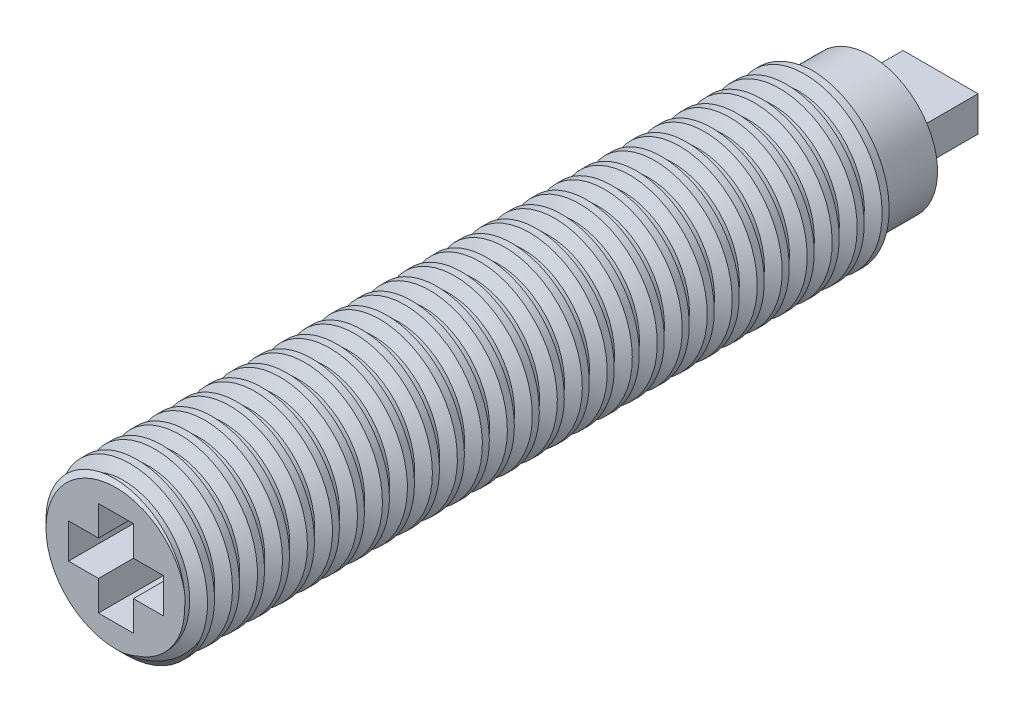
SolidWorks part; units mm, degrees
ref_plane "Front Plane" through (0, 0, 0) normal (0, 0, 1) x (1, 0, 0)
ref_plane "Top Plane" through (0, 0, 0) normal (0, 1, 0) x (1, 0, 0)
ref_plane "Right Plane" through (0, 0, 0) normal (1, 0, 0) x (0, 0, -1)
sketch "Sketch1" plane through (0, 0, 0) normal (0, 0, 1) x (1, 0, 0)
  circle A0 centre (0, 0) radius 8
  dimension "D1" = 16
extrude "Boss-Extrude1" add sketch "Sketch1" along normal blind 75.5
chamfer "Chamfer1" distance 1 angle 45 1 edges at (8, 0, 75.5)
ref_plane "Plane1" through (0, 0, 75.5) normal (0, 0, 1) x (1, 0, 0)
sketch "Sketch3" plane through (0, 0, 75.5) normal (0, 0, 1) x (1, 0, 0)
  circle A0 centre (0, 0) radius 8
sketch "Sketch4" plane through (0, 0, 0) normal (0, 1, 0) x (1, 0, 0)
  line L0 (-8.1701, -75.5) -> (-8.1701, -77.5)
  line L1 (-8.1701, -77.5) -> (-6.8701, -76.7494)
  line L2 (-6.8701, -76.7494) -> (-6.8701, -76.2506)
  line L3 (-6.8701, -76.2506) -> (-8.1701, -75.5)
  line L4 (-8, -74.5) -> (-8, -86.7444) construction
  line L5 (-8, -75.5) -> (8, -75.5) construction
  dimension "D1" = 2
  dimension "D2" = 1.3
  dimension "D3" = 60
curve "Helix/Spiral1" pitch 2.5 height 72.5 turns 29
sweep "Cut-Sweep2" cut profiles "Sketch4" path "Helix/Spiral1"
sketch "Sketch5" plane through (0, 0, 0) normal (0, 1, 0) x (1, 0, 0)
  line L0 (8, -2.1741) -> (8, 7.6033) construction
  line L1 (8, -4.3482) -> (8, 0) construction
  line L2 (8, 0) -> (-8, 0) construction
  line L3 (6.7, 0) -> (8, 0)
  line L4 (6.7, 0) -> (6.7, -5.5)
  line L5 (6.7, -5.5) -> (8, -5.5)
  line L6 (8, 0) -> (8, -5.5)
  dimension "D1" = 5.5
  dimension "D2" = 1.3
sweep "Cut-Sweep3" cut profiles "Sketch5" path edge at (8, 0, 0)
sketch "Sketch6" plane through (0, 0, 0) normal (0, 0, 1) x (1, 0, 0)
  line L1 (3.75, 1.75) -> (-3.75, 1.75)
  line L2 (3.75, 1.75) -> (3.75, -1.75)
  line L3 (3.75, -1.75) -> (-3.75, -1.75)
  line L4 (-3.75, 1.75) -> (-3.75, -1.75)
  point P4 (0, 1.75)
  point P5 (-3.75, 0)
  dimension "D1" = 7.5
  dimension "D2" = 3.5
extrude "Boss-Extrude2" add sketch "Sketch6" against normal blind 7
sketch "Sketch7" plane through (0, 0, 0) normal (0, 0, 1) x (1, 0, 0)
  text T0 "<b>CCW</b>" font "Century Gothic" height 2.5
extrude "Cut-Extrude1" cut sketch "Sketch7" along normal blind 1.5
sketch "Sketch8" plane through (0, 0, 75.5) normal (0, 0, 1) x (1, 0, 0)
  line L1 (-4.75, 1.75) -> (4.75, 1.75)
  line L2 (-4.75, 1.75) -> (-4.75, -1.75)
  line L3 (-4.75, -1.75) -> (4.75, -1.75)
  line L4 (4.75, 1.75) -> (4.75, -1.75)
  line L5 (-1.75, 4.75) -> (1.75, 4.75)
  line L6 (-1.75, 4.75) -> (-1.75, -4.75)
  line L7 (-1.75, -4.75) -> (1.75, -4.75)
  line L8 (1.75, 4.75) -> (1.75, -4.75)
  point P8 (0, 4.75)
  point P9 (0, 1.75)
  point P10 (4.75, 0)
  point P11 (1.75, 0)
  point P12 (0, 0)
  dimension "D1" = 3.5
  dimension "D2" = 3.5
  dimension "D3" = 9.5
  dimension "D4" = 9.5
extrude "Cut-Extrude2" cut sketch "Sketch8" against normal blind 11 contours L8 L5 L6 L1 | L8 L1 L6 L3 | L1 L8 L3 L4 | L6 L1 L2 L3 | L8 L3 L6 L7
